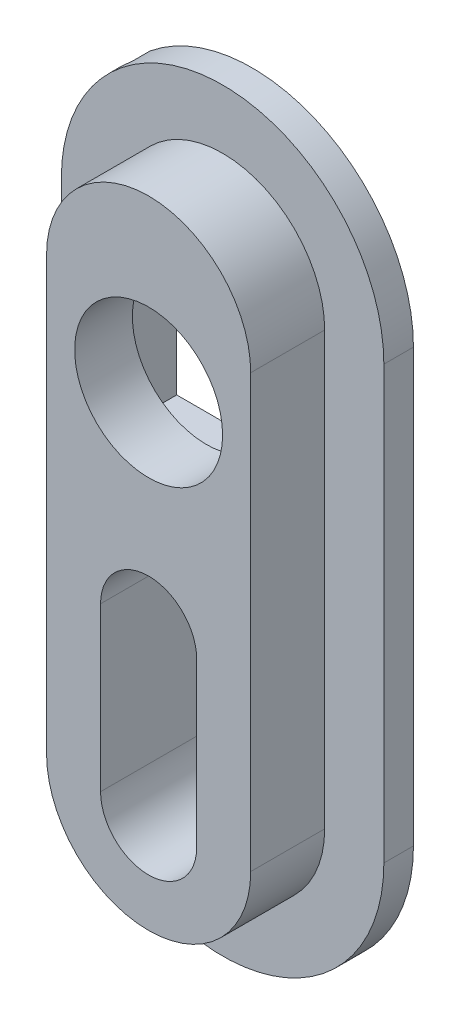
SolidWorks part; units mm, degrees
ref_plane "Front Plane" through (0, 0, 0) normal (1, 0, 0) x (0, 1, 0)
ref_plane "Top Plane" through (0, 0, 0) normal (0, 0, 1) x (0, 1, 0)
ref_plane "Right Plane" through (0, 0, 0) normal (0, 1, 0) x (-1, 0, 0)
ref_axis "x axis" through (-88.99, 0, 0) along (1, 0, 0)
ref_axis "y xxis" through (0, 88.99, 0) along (0, -1, 0)
ref_axis "z axis" through (0, 0, 55) along (0, 0, -1)
sketch "Sketch1" plane through (0, 0, 0) normal (0, 0, 1) x (0, 1, 0)
  line L0 (-7.3, 0) -> (7.3, 0) construction
  line L1 (-7.3, 3.45) -> (7.3, 3.45)
  line L2 (-7.3, -3.45) -> (7.3, -3.45)
  line L3 (-10.75, 3.6055) -> (-10.75, -3.6055) construction
  line L4 (10.75, 3.6055) -> (10.75, -3.6055) construction
  arc A0 (-7.3, 3.45) -> (-7.3, -3.45) centre (-7.3, 0) ccw
  arc A1 (7.3, -3.45) -> (7.3, 3.45) centre (7.3, 0) ccw
  point P3 (0, 0)
  point P10 (-10.75, 0)
  point P11 (-10.75, 0)
  point P16 (10.75, 0)
  point P17 (10.75, 0)
  dimension "D1" = 21.5
  dimension "D2" = 6.9
extrude "Boss-Extrude1" add sketch "Sketch1" against normal blind 2.5
sketch "Sketch3" plane through (0, 0, 0) normal (0, 0, 1) x (1, 0, 0)
  line L0 (0, -7.5) -> (0, -2) construction
  line L1 (-1.625, -7.5) -> (-1.625, -2)
  line L2 (1.625, -7.5) -> (1.625, -2)
  line L3 (-1.625, -9.125) -> (1.625, -9.125) construction
  line L4 (-1.625, -0.375) -> (1.625, -0.375) construction
  line L5 (0, 0) -> (0, 5) construction
  line L6 (2.55, 1.9) -> (-2.55, 1.9) construction
  line L7 (2.55, 1.9) -> (2.55, 8.1) construction
  line L8 (2.55, 8.1) -> (-2.55, 8.1) construction
  line L9 (-2.55, 1.9) -> (-2.55, 8.1) construction
  line L10 (2.55, 1.9) -> (-2.55, 8.1) construction
  line L11 (2.55, 8.1) -> (-2.55, 1.9) construction
  arc A0 (-1.625, -7.5) -> (1.625, -7.5) centre (0, -7.5) ccw
  arc A1 (1.625, -2) -> (-1.625, -2) centre (0, -2) ccw
  circle A2 centre (0, 5) radius 2.5
  point P3 (0, -4.75)
  point P12 (0, -9.125)
  point P13 (0, -9.125)
  point P14 (0, -0.375)
  point P15 (0, -0.375)
  dimension "D4" = 5
  dimension "D1" = 3.25
  dimension "D2" = 8.75
  dimension "D3" = 4.75
  dimension "D5" = 6.2
  dimension "D6" = 5.1
  dimension "D7" = 5
extrude "Cut-Extrude1" cut sketch "Sketch3" against normal blind 4
sketch "Sketch4" plane through (0, 0, -2.5) normal (0, 0, -1) x (1, 0, 0)
  line L0 (-5.45, 7.3) -> (-5.45, -7.3)
  line L1 (-5.45, 7.3) -> (5.45, 7.3) construction
  line L37 (1.625, 2) -> (1.625, 7.5)
  line L38 (-1.625, 7.5) -> (-1.625, 2)
  line L39 (1.625, 2) -> (1.625, 7.5)
  line L40 (-1.625, 7.5) -> (-1.625, 2)
  line L44 (-2.55, -1.9) -> (-2.55, -8.1)
  line L45 (-2.55, -8.1) -> (2.55, -8.1)
  line L46 (5.45, -7.3) -> (5.45, 7.3)
  line L47 (-5.45, 7.3) -> (-5.45, -7.3)
  line L48 (5.45, -7.3) -> (5.45, 7.3)
  line L50 (2.55, -8.1) -> (2.55, -1.9)
  line L51 (2.55, -1.9) -> (-2.55, -1.9)
  arc A40 (-1.625, 2) -> (1.625, 2) centre (0, 2) ccw
  arc A41 (1.625, 7.5) -> (-1.625, 7.5) centre (0, 7.5) ccw
  arc A42 (-1.625, 2) -> (1.625, 2) centre (0, 2) ccw
  arc A43 (1.625, 7.5) -> (-1.625, 7.5) centre (0, 7.5) ccw
  arc A52 (-5.45, -7.3) -> (5.45, -7.3) centre (0, -7.3) ccw
  arc A53 (5.45, 7.3) -> (-5.45, 7.3) centre (0, 7.3) ccw
  arc A54 (-5.45, -7.3) -> (5.45, -7.3) centre (0, -7.3) ccw
  arc A55 (5.45, 7.3) -> (-5.45, 7.3) centre (0, 7.3) ccw
  dimension "D4" = 14.6
  dimension "D1" = 0
  dimension "D3" = 2
extrude "Boss-Extrude2" add sketch "Sketch4" along normal blind 1
sketch "Sketch5" plane through (0, 0, -2.5) normal (0, 0, -1) x (1, 0, 0)
  line L1 (-2.55, -8.1) -> (2.55, -8.1)
  line L2 (-2.55, -8.1) -> (-2.55, -1.9)
  line L3 (-2.55, -1.9) -> (2.55, -1.9)
  line L4 (2.55, -8.1) -> (2.55, -1.9)
extrude "Cut-Extrude2" cut sketch "Sketch5" against normal offset from surface (0.55 mm away) 1.95 up to face at (0, -4.75, 0)
sketch "Sketch6" plane through (0, 0, -3.5) normal (0, 0, -1) x (1, 0, 0)
  line L0 (-5.45, -7.3) -> (-5.45, 7.3)
  line L1 (-3.45, 11.519) -> (-3.45, -11.519)
  line L3 (-3.45, -7.3) -> (-3.45, 7.3) construction
  arc A0 (-5.45, -7.3) -> (5.45, -7.3) centre (0, -7.3) ccw construction
  arc A1 (5.45, 7.3) -> (-5.45, 7.3) centre (0, 7.3) ccw construction
  arc A2 (-5.45, 7.3) -> (-3.45, 11.519) centre (0, 7.3) cw
  arc A3 (-5.45, -7.3) -> (-3.45, -11.519) centre (0, -7.3) ccw
extrude "Cut-Extrude3" cut sketch "Sketch6" against normal offset from surface (0.6 mm away) 0.4 up to face at (0, 0, -2.5)
